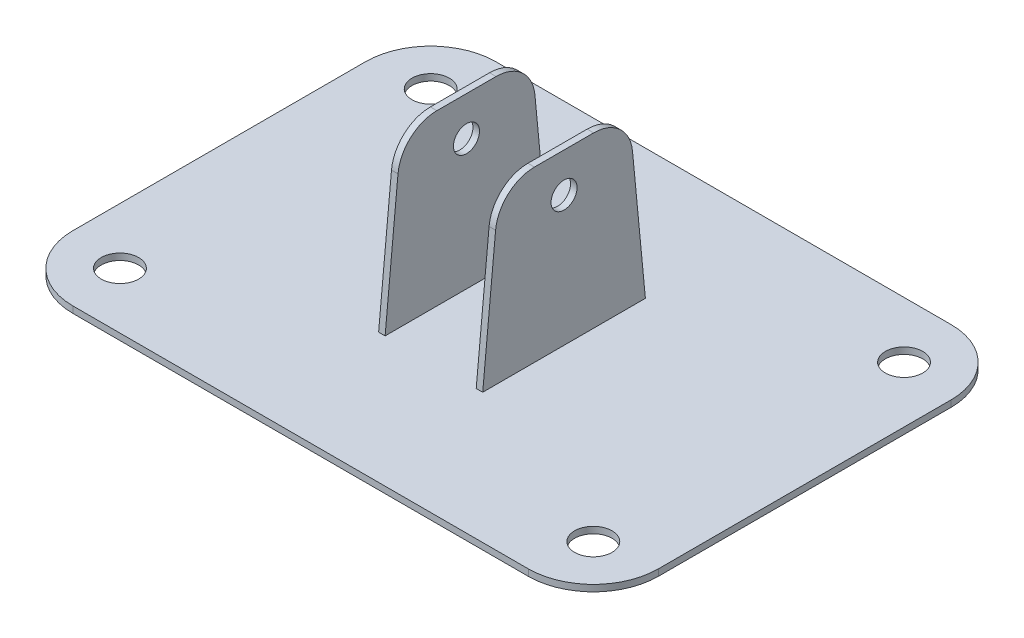
SolidWorks part; units mm, degrees
material "ABS"
ref_plane "Front Plane" through (0, 0, 0) normal (0, 0, 1) x (1, 0, 0)
ref_plane "Top Plane" through (0, 0, 0) normal (0, 1, 0) x (1, 0, 0)
ref_plane "Right Plane" through (0, 0, 0) normal (1, 0, 0) x (0, 0, -1)
sketch "Sketch1" plane through (0, 0, 0) normal (0, 1, 0) x (1, 0, 0)
  line L0 (-45, 0) -> (45, 0) construction
  line L1 (-45, -32.5) -> (45, -32.5)
  line L2 (-45, -32.5) -> (-45, 32.5)
  line L3 (-45, 32.5) -> (45, 32.5)
  line L4 (45, -32.5) -> (45, 32.5)
  line L5 (-45, -32.5) -> (45, 32.5) construction
  line L6 (-45, 32.5) -> (45, -32.5) construction
  line L7 (0, 32.5) -> (0, -32.5) construction
  line L8 (-36.375, 23.875) -> (36.375, 23.875) construction
  line L9 (-36.375, 23.875) -> (-36.375, -23.875) construction
  line L10 (-36.375, -23.875) -> (36.375, -23.875) construction
  circle A0 centre (-36.375, 23.875) radius 2.875
  circle A1 centre (36.375, 23.875) radius 2.875
  circle A2 centre (36.375, -23.875) radius 2.875
  circle A3 centre (-36.375, -23.875) radius 2.875
  point P0 (0, 0)
  point P14 (0, 23.875)
  point P16 (-36.375, 21)
  point P20 (-36.375, 0)
  point P21 (-36.375, -21)
  point P22 (-33.5, 23.875)
  point P23 (33.5, 23.875)
  dimension "D3" = 5.75
  dimension "D1" = 90
  dimension "D2" = 65
  dimension "D4" = 42
  dimension "D5" = 67
extrude "Boss-Extrude1" add sketch "Sketch1" along normal blind 1
fillet "Fillet1" radius 10 4 edges at (-45, 0.5, 32.5) (-45, 0.5, -32.5) (45, 0.5, -32.5) (45, 0.5, 32.5)
sketch "Sketch2" plane through (45, 0, 0) normal (1, 0, 0) x (0, 0, -1)
  line L0 (0, 0) -> (0, 35.2542) construction
  line L1 (-12.5, 1) -> (-10, 27)
  line L2 (-22.5, 1) -> (22.5, 1) construction
  line L3 (-10, 27) -> (10, 27)
  line L4 (0, 21) -> (-10.5769, 21) construction
  line L5 (12.5, 1) -> (10, 27)
  line L6 (-12.5, 1) -> (12.5, 1)
  circle A0 centre (0, 21) radius 2
  point P12 (0, 27)
  dimension "D4" = 6
  dimension "D5" = 4
  dimension "D1" = 25
  dimension "D2" = 26
  dimension "D3" = 20
extrude "Boss-Extrude2" add sketch "Sketch2" against normal blind 1 from offset 37 offset against normal yes
fillet "Fillet2" radius 6 2 edges at (7.5, 27, 10) (7.5, 27, -10)
ref_plane "Plane1" through (0, 0, 0) normal (-1, 0, 0) x (0, 0, 1)
mirror "Mirror1" about plane through (0, 0, 0) normal (-1, 0, 0) of "Boss-Extrude2", "Fillet2"
